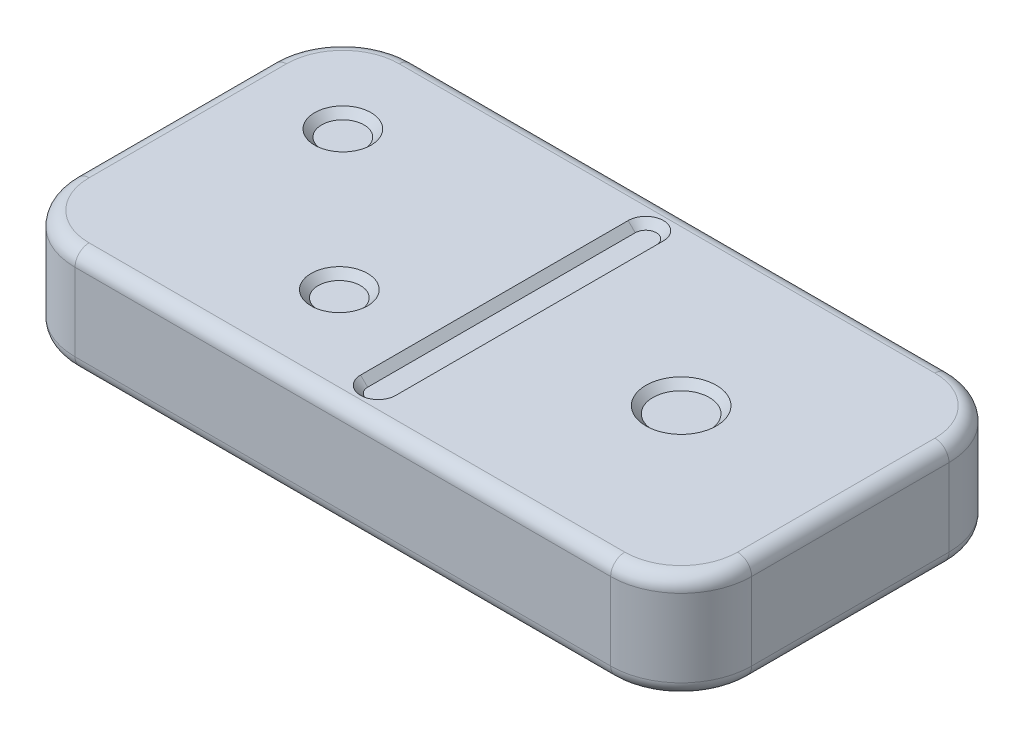
SolidWorks part; units mm, degrees
material "ABS"
ref_plane "Front Plane" through (0, 0, 0) normal (0, 0, 1) x (1, 0, 0)
ref_plane "Top Plane" through (0, 0, 0) normal (0, 1, 0) x (1, 0, 0)
ref_plane "Right Plane" through (0, 0, 0) normal (1, 0, 0) x (0, 0, -1)
sketch "Esquisse1" plane through (0, 0, 0) normal (0, 1, 0) x (1, 0, 0)
  line L1 (0, 0) -> (48, 0)
  line L2 (0, 0) -> (0, 24)
  line L3 (0, 24) -> (48, 24)
  line L4 (48, 0) -> (48, 24)
  dimension "D1" = 48
  dimension "D2" = 24
extrude "Extrusion1" add sketch "Esquisse1" along normal blind 7.5
fillet "Congé2" radius 5 4 edges at (48, 3.75, 0) (48, 3.75, -24) (0, 3.75, 0) (0, 3.75, -24)
fillet "Congé5" radius 1 8 edges at (46.5355, 7.5, -22.5355) (48, 7.5, -12) (46.5355, 7.5, -1.4645) (24, 7.5, 0) (1.4645, 7.5, -1.4645) (0, 7.5, -12) (1.4645, 7.5, -22.5355) (24, 7.5, -24)
fillet "Congé6" radius 1 8 edges at (46.5355, 0, -22.5355) (48, 0, -12) (46.5355, 0, -1.4645) (24, 0, 0) (1.4645, 0, -1.4645) (0, 0, -12) (1.4645, 0, -22.5355) (24, 0, -24)
sketch "Esquisse4" plane through (0, 7.5, 0) normal (0, 1, 0) x (1, 0, 0)
  line L0 (1, 12) -> (47, 12) construction
  line L1 (1, 19) -> (1, 5) construction
  line L2 (47, 5) -> (47, 19) construction
  line L3 (24, 23) -> (24, 1) construction
  line L4 (43, 23) -> (5, 23) construction
  line L5 (5, 1) -> (43, 1) construction
  line L7 (23.75, 21.4914) -> (24.25, 21.4914)
  line L8 (23.75, 21.4914) -> (23.75, 2.5086)
  line L9 (23.75, 2.5086) -> (24.25, 2.5086)
  line L10 (24.25, 21.4914) -> (24.25, 2.5086)
  line L11 (23.75, 21.4914) -> (24.25, 2.5086) construction
  line L12 (23.75, 2.5086) -> (24.25, 21.4914) construction
  point P12 (24, 12)
  dimension "D1" = 0.5
extrude "Extrusion2" cut sketch "Esquisse4" against normal blind 0.5
sketch "Esquisse5" plane through (0, 7.5, 0) normal (0, 1, 0) x (1, 0, 0)
  line L0 (24.25, 21.4914) -> (23.75, 21.4914) construction
  line L1 (23.75, 2.5086) -> (24.25, 2.5086) construction
  circle A0 centre (24, 21.4914) radius 0.25
  circle A1 centre (24, 2.5086) radius 0.25
  dimension "D1" = 0.5
  dimension "D2" = 0.5
extrude "Extrusion3" cut sketch "Esquisse5" against normal blind 0.5
chamfer "Chanfrein1" distance 1 angle 45 4 edges at (24, 7.5, -21.7414) (24.25, 7.5, -12) (24, 7.5, -2.2586) (23.75, 7.5, -12)
sketch "Esquisse10" plane through (0, 7.5, 0) normal (0, 1, 0) x (1, 0, 0)
  line L0 (1, 19) -> (1, 5) construction
  line L1 (22.75, 2.5086) -> (22.75, 21.4914) construction
  line L2 (43, 23) -> (5, 23) construction
  line L3 (5, 1) -> (43, 1) construction
  circle A0 centre (7, 17) radius 2
  circle A1 centre (16.75, 7) radius 2
  dimension "D1" = 4
  dimension "D2" = 4
  dimension "D3" = 6
  dimension "D4" = 6
  dimension "D5" = 6
  dimension "D6" = 6
extrude "Extrusion7" cut sketch "Esquisse10" against normal blind 0.5 draft 45
sketch "Esquisse11" plane through (0, 7.5, 0) normal (0, 1, 0) x (1, 0, 0)
  line L0 (47, 5) -> (47, 19) construction
  line L1 (5, 1) -> (43, 1) construction
  circle A0 centre (36, 12) radius 2.5
  dimension "D1" = 5
  dimension "D2" = 11
  dimension "D3" = 11
extrude "Extrusion8" cut sketch "Esquisse11" against normal blind 0.5 draft 45
